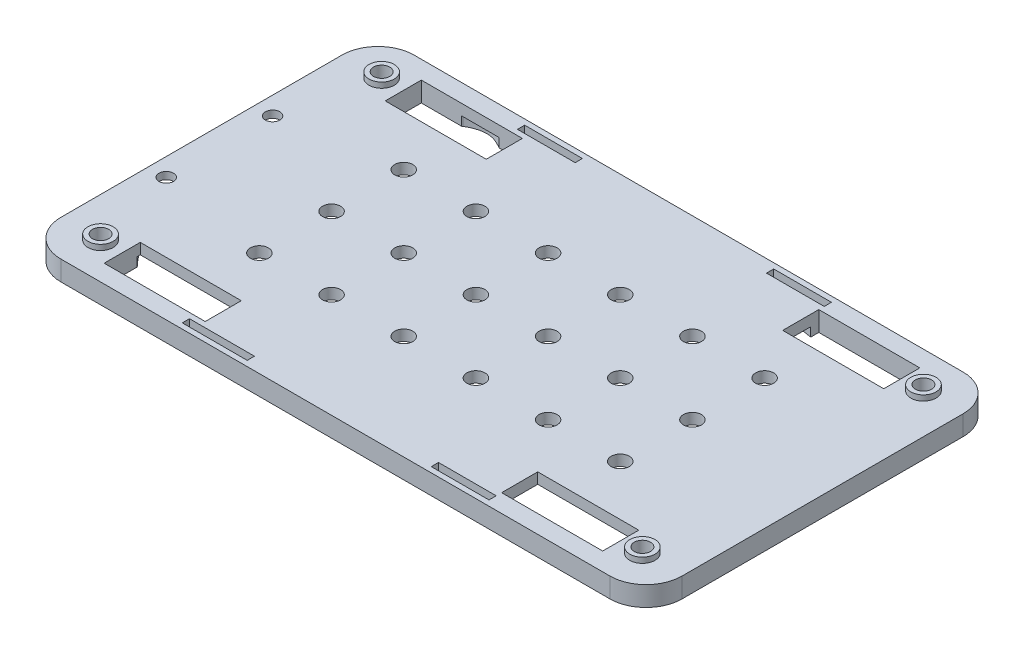
SolidWorks part; units mm, degrees
ref_plane "Front Plane" through (0, 0, 0) normal (0, 0, 1) x (1, 0, 0)
ref_plane "Top Plane" through (0, 0, 0) normal (0, 1, 0) x (1, 0, 0)
ref_plane "Right Plane" through (0, 0, 0) normal (1, 0, 0) x (0, 0, -1)
sketch "Sketch1" plane through (0, 0, 0) normal (0, 1, 0) x (1, 0, 0)
  line L1 (-78.1571, 35.933) -> (-78.1571, -14.1122)
  line L2 (78.9797, 0.0343) -> (-78.1571, 0.0343) construction
  line L3 (-77.1571, 35.7646) -> (-77.1571, -14.1122)
  line L4 (78.9797, -0.9657) -> (-78.1571, -0.9657)
  arc A1 (37.8695, -35.2975) -> (39.5975, -35.2134) centre (38.2635, -25.6055) ccw
  arc A2 (37.9263, -34.299) -> (39.4753, -34.2207) centre (38.2635, -25.6055) ccw
  spline S0 degree 1 poles (-77.1571, -14.1122) (-56.919, -31.9168) knots 0 0 1 1 construction
  spline S1 degree 1 poles (-56.919, -31.9168) (37.9263, -34.299) knots 0 0 1 1 construction
  spline S2 degree 1 poles (39.4753, -34.2207) (77.9849, 0.1477) knots 0 0 1 1 construction
  spline S3 degree 1 poles (77.9849, 0.1477) (25.0602, 52.8732) knots 0 0 1 1 construction
  spline S4 degree 1 poles (25.0602, 52.8732) (-5.6593, 44.1904) knots 0 0 1 1 construction
  spline S5 degree 1 poles (-5.6593, 44.1904) (-43.9853, 50.6886) knots 0 0 1 1 construction
  spline S6 degree 1 poles (-43.9853, 50.6886) (-59.7702, 54.7238) knots 0 0 1 1 construction
  spline S7 degree 1 poles (-59.7702, 54.7238) (-74.5158, 41.0521) knots 0 0 1 1 construction
  spline S8 degree 1 poles (-74.5158, 41.0521) (-77.1571, 35.7646) knots 0 0 1 1 construction
  spline S9 degree 3 poles (-77.1571, -14.1122) (-77.1565, -14.3701) (-77.1092, -14.8732) (-76.8359, -15.9559) (-76.1879, -17.5008) (-75.044, -19.4183) (-73.152, -22.0092) (-70.3495, -25.0822) (-66.8736, -28.0972) (-63.6864, -30.2141) (-61.0019, -31.4062) (-58.8274, -31.848) (-57.5718, -31.8794) (-56.919, -31.9168) knots 0.000484 0.000484 0.000484 0.000484 0.031521 0.062558 0.124632 0.186706 0.248781 0.372929 0.497077 0.621225 0.745373 0.869521 0.993669 0.993669 0.993669 0.993669
  spline S10 degree 3 poles (-56.919, -31.9168) (-56.6769, -31.8873) (-56.2021, -31.8274) (-55.1791, -31.687) (-53.8294, -31.4877) (-52.0759, -31.2184) (-49.5744, -30.8354) (-46.1465, -30.3372) (-41.5825, -29.7813) (-36.5976, -29.3261) (-29.4274, -28.913) (-19.5571, -28.8468) (-6.4839, -29.5875) (5.2448, -30.7865) (15.023, -31.9295) (22.521, -32.809) (30.1538, -33.642) (35.3408, -34.1075) (37.9263, -34.299) knots 0.000538 0.000538 0.000538 0.000538 0.016152 0.031766 0.062993 0.094221 0.125449 0.187904 0.250359 0.312815 0.37527 0.50018 0.625091 0.750001 0.812457 0.874912 0.937367 0.999822 0.999822 0.999822 0.999822
  spline S11 degree 3 poles (39.4753, -34.2207) (41.0079, -34.0574) (44.09, -33.7147) (50.0835, -32.8429) (57.0969, -31.1859) (64.2184, -27.8839) (69.7763, -23.1857) (73.0497, -18.2789) (74.9177, -14.0269) (75.9805, -10.7732) (76.7509, -7.5724) (77.1995, -5.064) (77.4798, -3.2279) (77.6607, -1.9649) (77.8261, -0.8108) (77.9301, -0.1834) (77.9849, 0.1477) knots -0.000309 -0.000309 -0.000309 -0.000309 0.063093 0.126495 0.253299 0.380104 0.506908 0.633712 0.697114 0.760516 0.823918 0.88732 0.919021 0.950722 0.982423 1.014124 1.014124 1.014124 1.014124
  spline S12 degree 3 poles (77.9849, 0.1477) (78.0286, 1.2633) (78.0637, 3.5224) (77.9426, 6.757) (77.6596, 9.9047) (77.0733, 13.9671) (75.9626, 18.7836) (73.4433, 25.9357) (69.0206, 33.8098) (62.0495, 41.4932) (53.7895, 47.3444) (44.6121, 51.2947) (34.9036, 53.2804) (28.3113, 53.2357) (25.0602, 52.8732) knots 0.000169 0.000169 0.000169 0.000169 0.031414 0.062658 0.093902 0.125147 0.187635 0.250124 0.375101 0.500079 0.625056 0.750034 0.875011 0.999988 0.999988 0.999988 0.999988
  spline S13 degree 3 poles (25.0602, 52.8732) (19.8954, 51.6294) (12.3224, 49.1317) (2.1607, 45.9713) (-3.0371, 44.6913) (-5.6593, 44.1904) knots 0.000659 0.000659 0.000659 0.000659 0.498067 0.746772 0.995476 0.995476 0.995476 0.995476
  spline S14 degree 3 poles (-5.6593, 44.1904) (-6.6879, 44.0461) (-8.7287, 43.7719) (-12.9633, 43.2668) (-18.1826, 42.7952) (-23.9015, 42.6322) (-28.8306, 42.9899) (-32.9666, 43.9514) (-35.9177, 45.2914) (-38.1959, 46.6779) (-39.9392, 47.8658) (-41.507, 48.9798) (-42.8638, 49.9292) (-43.6163, 50.4405) (-43.9853, 50.6886) knots -0.000196 -0.000196 -0.000196 -0.000196 0.062587 0.12537 0.250936 0.376501 0.502067 0.627632 0.753198 0.815981 0.878764 0.941546 0.972938 1.004329 1.004329 1.004329 1.004329
  spline S15 degree 3 poles (-43.9853, 50.6886) (-44.2445, 50.8673) (-44.7682, 51.2325) (-45.7507, 51.9331) (-46.8912, 52.7591) (-48.146, 53.6496) (-49.6971, 54.6811) (-51.4608, 55.6487) (-53.4077, 56.2593) (-55.2517, 56.3574) (-56.711, 56.0808) (-57.7948, 55.7138) (-58.5465, 55.3915) (-59.2299, 55.0428) (-59.5837, 54.8359) (-59.7702, 54.7238) knots -0.002497 -0.002497 -0.002497 -0.002497 0.029066 0.060629 0.123754 0.18688 0.250006 0.376257 0.502509 0.62876 0.755012 0.818137 0.881263 0.944389 1.007515 1.007515 1.007515 1.007515
  spline S16 degree 3 poles (-78.1571, -14.1122) (-78.1559, -14.7524) (-77.9173, -15.9777) (-77.0678, -17.9828) (-75.8538, -20.0098) (-73.8827, -22.6985) (-70.9901, -25.8584) (-67.4096, -28.9504) (-64.0991, -31.1349) (-61.2379, -32.3904) (-59.243, -32.7789) (-57.8421, -32.8756) (-57.2118, -32.9007) (-56.8882, -32.9203) knots 0.000409 0.000409 0.000409 0.000409 0.062843 0.125276 0.18771 0.250143 0.375011 0.499878 0.624745 0.749612 0.874479 0.936913 0.999346 0.999346 0.999346 0.999346
  spline S17 degree 3 poles (-56.8882, -32.9203) (-56.6427, -32.8908) (-56.1603, -32.8306) (-55.1309, -32.6904) (-53.7754, -32.491) (-52.0233, -32.2221) (-49.5292, -31.8398) (-46.1189, -31.3427) (-41.5829, -30.7872) (-36.6286, -30.3313) (-29.4997, -29.9158) (-19.6749, -29.8441) (-6.6369, -30.5782) (5.0856, -31.7749) (14.8757, -32.919) (22.3927, -33.8009) (30.0532, -34.6371) (35.2704, -35.1052) (37.8695, -35.2975) knots -0.001373 -0.001373 -0.001373 -0.001373 0.014273 0.029919 0.06121 0.092502 0.123794 0.186377 0.24896 0.311543 0.374127 0.499293 0.62446 0.749626 0.81221 0.874793 0.937376 0.99996 0.99996 0.99996 0.99996
  spline S18 degree 3 poles (39.5975, -35.2134) (41.1398, -35.049) (44.2356, -34.7045) (50.3018, -33.8209) (57.4502, -32.1301) (64.7991, -28.7164) (70.5782, -23.8111) (73.9656, -18.7006) (75.8832, -14.3057) (76.9672, -10.962) (77.7479, -7.6914) (78.1997, -5.145) (78.4804, -3.2966) (78.6613, -2.0308) (78.824, -0.9009) (78.9276, -0.2806) (78.9816, 0.0458) knots -0.000086 -0.000086 -0.000086 -0.000086 0.063428 0.126941 0.253967 0.380993 0.50802 0.635046 0.698559 0.762072 0.825585 0.889098 0.920855 0.952612 0.984368 1.016125 1.016125 1.016125 1.016125
  spline S19 degree 3 poles (78.9816, 0.0458) (79.0271, 1.1797) (79.0647, 3.4739) (78.9444, 6.7697) (78.6587, 9.9749) (78.0642, 14.1169) (76.9341, 19.0326) (74.3646, 26.3398) (69.8439, 34.3944) (62.712, 42.2543) (54.2626, 48.2351) (44.8799, 52.2671) (34.9529, 54.2886) (28.2109, 54.2351) (24.8869, 53.8601) knots -0.000407 -0.000407 -0.000407 -0.000407 0.03088 0.062166 0.093453 0.12474 0.187314 0.249888 0.375035 0.500183 0.62533 0.750478 0.875625 1.000773 1.000773 1.000773 1.000773
  spline S20 degree 3 poles (24.8869, 53.8601) (22.2839, 53.2349) (17.1223, 51.77) (6.9788, 48.4835) (-0.6206, 46.1711) (-5.8226, 45.1772) knots -0.001281 -0.001281 -0.001281 -0.001281 0.247714 0.49671 0.9947 0.9947 0.9947 0.9947
  spline S21 degree 3 poles (-5.8226, 45.1772) (-6.8463, 45.0337) (-8.8779, 44.761) (-13.0882, 44.2593) (-18.2643, 43.7927) (-23.9018, 43.6338) (-28.7026, 43.9859) (-32.6523, 44.9085) (-35.4477, 46.177) (-37.6484, 47.5152) (-39.3619, 48.6824) (-40.9248, 49.793) (-42.292, 50.7496) (-43.0505, 51.2651) (-43.4225, 51.5151) knots 0.000305 0.000305 0.000305 0.000305 0.063048 0.125791 0.251276 0.376761 0.502247 0.627732 0.753218 0.815961 0.878703 0.941446 0.972817 1.004189 1.004189 1.004189 1.004189
  spline S22 degree 3 poles (-43.4225, 51.5151) (-43.6786, 51.6918) (-44.1958, 52.0526) (-45.1684, 52.7462) (-46.308, 53.5714) (-47.577, 54.4721) (-49.1727, 55.5335) (-51.0441, 56.5648) (-53.2147, 57.2519) (-55.3195, 57.3652) (-56.9568, 57.0533) (-58.1477, 56.6506) (-58.9689, 56.2985) (-59.5708, 55.992) (-60.0059, 55.7483) (-60.1862, 55.6406) (-60.2803, 55.5839) knots -0.002294 -0.002294 -0.002294 -0.002294 0.029245 0.060783 0.12386 0.186936 0.250013 0.376167 0.50232 0.628473 0.754627 0.817704 0.88078 0.943857 0.975396 1.006934 1.006934 1.006934 1.006934
  spline S23 degree 3 poles (-60.2803, 55.5839) (-60.715, 55.3297) (-61.582, 54.801) (-63.2222, 53.7187) (-65.9105, 51.7373) (-69.2431, 48.741) (-72.0244, 45.6929) (-73.7392, 43.6279) (-74.6657, 42.4756) (-75.1049, 41.9202) (-75.3265, 41.639) knots 0.000427 0.000427 0.000427 0.000427 0.063268 0.126109 0.251792 0.503158 0.754524 0.880206 0.943048 1.005889 1.005889 1.005889 1.005889
  spline S24 degree 3 poles (-59.7702, 54.7238) (-60.1936, 54.4761) (-61.0386, 53.9612) (-62.6368, 52.9072) (-65.2587, 50.9763) (-68.5171, 48.0498) (-71.2443, 45.0657) (-73.1899, 42.7247) (-74.0698, 41.6179) (-74.5158, 41.0521) knots 0.000174 0.000174 0.000174 0.000174 0.062881 0.125589 0.251004 0.501833 0.752662 0.878077 1.003492 1.003492 1.003492 1.003492
  spline S25 degree 3 poles (-74.5158, 41.0521) (-75.0658, 40.2217) (-76.0765, 38.4779) (-76.8336, 36.6875) (-77.1571, 35.7646) knots 0.499549 0.499549 0.499549 0.499549 0.499766 0.499983 0.499983 0.499983 0.499983
  spline S26 degree 3 poles (-75.3265, 41.639) (-75.92, 40.746) (-77.0064, 38.8701) (-77.815, 36.9314) (-78.1571, 35.933) knots 0.499546 0.499546 0.499546 0.499546 0.49977 0.499995 0.499995 0.499995 0.499995
  point P0 (0.4631, 0.0343)
  dimension "D1" = 1
sketch "Sketch6" plane through (0, 0, 0) normal (0, 1, 0) x (1, 0, 0)
  line L0 (-78.1571, 35.933) -> (-78.1571, -14.1122) construction
  line L1 (73.9816, 59.5839) -> (-78.1571, 59.5839)
  line L2 (83.9816, 49.5839) -> (83.9816, -28.2975)
  line L3 (73.9816, -38.2975) -> (-78.1571, -38.2975)
  line L4 (-88.1571, 49.5839) -> (-88.1571, -28.2975)
  arc A0 (-78.1571, -38.2975) -> (-88.1571, -28.2975) centre (-78.1571, -28.2975) cw
  arc A1 (-88.1571, 49.5839) -> (-78.1571, 59.5839) centre (-78.1571, 49.5839) cw
  arc A2 (73.9816, 59.5839) -> (83.9816, 49.5839) centre (73.9816, 49.5839) cw
  arc A3 (83.9816, -28.2975) -> (73.9816, -38.2975) centre (73.9816, -28.2975) cw
  dimension "D5" = 10
  dimension "D1" = 5
  dimension "D2" = 10
  dimension "D3" = 3
  dimension "D4" = 4
extrude "Boss-Extrude2" add sketch "Sketch6" along normal blind 6.5
extrude "Cut-Extrude1" cut sketch "Sketch1" along normal blind 2.5 contours A2 S11 L4 L3 S9 S10 | S24 S25 L3 L4 S11 S12 S13 S14 S15 region at (0.1139, 0, 15.5782) region at (-2.2602, 0, -23.2786)
sketch "Sketch7" plane through (0, 0, 0) normal (0, -1, 0) x (1, 0, 0)
  line L1 (-76.2189, 14.1122) -> (-91.3452, 14.1122)
  line L2 (-76.2189, 14.1122) -> (-76.2189, -35.933)
  line L3 (-76.2189, -35.933) -> (-91.3452, -35.933)
  line L4 (-91.3452, 14.1122) -> (-91.3452, -35.933)
extrude "Cut-Extrude2" cut sketch "Sketch7" against normal up to surface (2.5 mm away) contours L2 L1 L4 L3 up to face at (-19.4492, 2.5, -12.7234)
sketch "Sketch8" plane through (0, 6.5, 0) normal (0, 1, 0) x (1, 0, 0)
  line L0 (83.9816, 10.6432) -> (-88.1571, 10.6432) construction
  line L1 (83.9816, -28.2975) -> (83.9816, 49.5839) construction
  line L2 (-88.1571, 49.5839) -> (-88.1571, -28.2975) construction
  line L3 (-2.0877, 59.5839) -> (-2.0877, -38.2975) construction
  line L4 (73.9816, 59.5839) -> (-78.1571, 59.5839) construction
  line L5 (-78.1571, -38.2975) -> (73.9816, -38.2975) construction
  line L7 (78.9816, 54.5839) -> (38.9816, 54.5839)
  line L8 (78.9816, 54.5839) -> (78.9816, 44.5839)
  line L9 (78.9816, 44.5839) -> (38.9816, 44.5839)
  line L10 (38.9816, 54.5839) -> (38.9816, 44.5839)
  line L22 (38.9816, 49.5839) -> (78.9816, 49.5839) construction
  line L23 (66.9816, 54.5839) -> (66.9816, 44.5839)
  circle A1 centre (72.9816, 49.5839) radius 3.5
  dimension "D6" = 7
  dimension "D1" = 10
  dimension "D2" = 40
  dimension "D3" = 5
  dimension "D4" = 5
  dimension "D5" = 6
  dimension "D7" = 6
sketch "Sketch9" plane through (0, 0, 0) normal (0, -1, 0) x (1, 0, 0)
  circle A0 centre (72.9816, -49.5839) radius 4.5
  dimension "D1" = 9
extrude "Cut-Extrude5" cut sketch "Sketch9" against normal blind 3.5
sketch "Sketch10" plane through (0, 3.5, 0) normal (0, -1, 0) x (1, 0, 0)
  circle A0 centre (72.9816, -49.5839) radius 2.25
  dimension "D1" = 4.5
extrude "Cut-Extrude6" cut sketch "Sketch10" against normal blind 21
extrude "Cut-Extrude8" cut sketch "Sketch8" against normal blind 42 contours L23 L7 L10 L9 region at (52.9816, 6.5, -49.5839)
extrude "Cut-Extrude9" cut sketch "Sketch8<3>" against normal blind 1 contours L7 L23 L9 L8 A1 region at (78.8254, 6.5, -49.5839)
sketch "Sketch8<3>" plane through (0, 6.5, 0) normal (0, 1, 0) x (1, 0, 0) same geometry as "Sketch8"
sketch "Sketch12" plane through (0, 6.5, 0) normal (0, 1, 0) x (1, 0, 0)
  line L0 (-88.1571, 10.6432) -> (83.9816, 10.6432) construction
  line L1 (-88.1571, 49.5839) -> (-88.1571, -28.2975) construction
  line L2 (83.9816, -28.2975) -> (83.9816, 49.5839) construction
  line L3 (-2.0877, 59.5839) -> (-2.0877, -36.8461) construction
  line L4 (73.9816, 59.5839) -> (-78.1571, 59.5839) construction
ref_plane "Plane1" through (0, 0, -10.6432) normal (0, 0, 1) x (1, 0, 0)
ref_plane "Plane2" through (-2.0877, 0, 0) normal (-1, 0, 0) x (0, 0, 1)
mirror "Mirror1" about plane through (0, 0, -10.6432) normal (0, 0, 1) of "Cut-Extrude5", "Cut-Extrude6", "Cut-Extrude8", "Cut-Extrude9"
mirror "Mirror2" about plane through (-2.0877, 0, 0) normal (-1, 0, 0) of "Mirror1", "Cut-Extrude9", "Cut-Extrude8", "Cut-Extrude6", "Cut-Extrude5"
sketch "Sketch13" plane through (0, 6.5, 0) normal (0, 1, 0) x (1, 0, 0)
  line L0 (-83.1571, 44.5839) -> (-43.1571, 44.5839) construction
  line L1 (58.9816, 39.5839) -> (-63.1571, 39.5839)
  line L2 (58.9816, 39.5839) -> (58.9816, -18.2975)
  line L3 (58.9816, -18.2975) -> (-63.1571, -18.2975)
  line L4 (-63.1571, 39.5839) -> (-63.1571, -18.2975)
  line L5 (58.9816, 39.5839) -> (-63.1571, -18.2975) construction
  line L6 (58.9816, -18.2975) -> (-63.1571, 39.5839) construction
  line L7 (-83.1571, -23.2975) -> (-43.1571, -23.2975) construction
  line L8 (83.9816, -28.2975) -> (83.9816, 49.5839) construction
  line L9 (-88.1571, 49.5839) -> (-88.1571, -28.2975) construction
  point P0 (-2.0877, 10.6432)
  dimension "D1" = 5
  dimension "D2" = 5
  dimension "D3" = 25
  dimension "D4" = 25
extrude "Cut-Extrude10" cut sketch "Sketch13" against normal blind 1
sketch "Sketch14" plane through (0, 5.5, 0) normal (0, 1, 0) x (1, 0, 0)
  line L0 (-63.1571, 10.6432) -> (58.9816, 10.6432) construction
  line L1 (-63.1571, 39.5839) -> (-63.1571, -18.2975) construction
  line L2 (58.9816, -18.2975) -> (58.9816, 39.5839) construction
  line L3 (-63.1571, -9.3568) -> (58.9816, -9.3568) construction
  line L4 (-63.1571, 10.6432) -> (58.9816, 10.6432) construction
  line L5 (-63.1571, 30.6432) -> (58.9816, 30.6432) construction
  circle A1 centre (-12.0877, 10.6432) radius 2.5
  circle A2 centre (-32.0877, 10.6432) radius 2.5
  circle A3 centre (-52.0877, 10.6432) radius 2.5
  circle A4 centre (-12.0877, 10.6432) radius 2.5
  circle A5 centre (-32.0877, 10.6432) radius 2.5
  circle A6 centre (7.9123, 10.6432) radius 2.5
  circle A7 centre (-12.0877, 10.6432) radius 2.5
  circle A8 centre (27.9123, 10.6432) radius 2.5
  circle A9 centre (7.9123, 10.6432) radius 2.5
  circle A10 centre (7.9123, 10.6432) radius 2.5
  circle A11 centre (27.9123, 10.6432) radius 2.5
  circle A12 centre (47.9123, 10.6432) radius 2.5
  circle A13 centre (-12.0877, -9.3568) radius 2.5
  circle A14 centre (-32.0877, -9.3568) radius 2.5
  circle A15 centre (-52.0877, -9.3568) radius 2.5
  circle A16 centre (-12.0877, -9.3568) radius 2.5
  circle A17 centre (-32.0877, -9.3568) radius 2.5
  circle A18 centre (7.9123, -9.3568) radius 2.5
  circle A19 centre (-12.0877, -9.3568) radius 2.5
  circle A20 centre (27.9123, -9.3568) radius 2.5
  circle A21 centre (7.9123, -9.3568) radius 2.5
  circle A22 centre (7.9123, -9.3568) radius 2.5
  circle A23 centre (27.9123, -9.3568) radius 2.5
  circle A24 centre (47.9123, -9.3568) radius 2.5
  circle A25 centre (-12.0877, 10.6432) radius 2.5
  circle A26 centre (-32.0877, 10.6432) radius 2.5
  circle A27 centre (-52.0877, 10.6432) radius 2.5
  circle A28 centre (-12.0877, 10.6432) radius 2.5
  circle A29 centre (-32.0877, 10.6432) radius 2.5
  circle A30 centre (7.9123, 10.6432) radius 2.5
  circle A31 centre (-12.0877, 10.6432) radius 2.5
  circle A32 centre (27.9123, 10.6432) radius 2.5
  circle A33 centre (7.9123, 10.6432) radius 2.5
  circle A34 centre (7.9123, 10.6432) radius 2.5
  circle A35 centre (27.9123, 10.6432) radius 2.5
  circle A36 centre (47.9123, 10.6432) radius 2.5
  circle A37 centre (-12.0877, 30.6432) radius 2.5
  circle A38 centre (-32.0877, 30.6432) radius 2.5
  circle A39 centre (-52.0877, 30.6432) radius 2.5
  circle A40 centre (-12.0877, 30.6432) radius 2.5
  circle A41 centre (-32.0877, 30.6432) radius 2.5
  circle A42 centre (7.9123, 30.6432) radius 2.5
  circle A43 centre (-12.0877, 30.6432) radius 2.5
  circle A44 centre (27.9123, 30.6432) radius 2.5
  circle A45 centre (7.9123, 30.6432) radius 2.5
  circle A46 centre (7.9123, 30.6432) radius 2.5
  circle A47 centre (27.9123, 30.6432) radius 2.5
  circle A48 centre (47.9123, 30.6432) radius 2.5
  point P8 (-2.0877, 10.6432)
  point P37 (-2.0877, -9.3568)
  point P64 (-2.0877, 10.6432)
  point P91 (-2.0877, 30.6432)
  dimension "D2" = 5
  dimension "D1" = 10
  dimension "D3" = 3
  dimension "D4" = 4
  dimension "D5" = 2
  dimension "D6" = 2
extrude "Cut-Extrude11" cut sketch "Sketch14" against normal blind 57 contours A39 | A42 | A44 | A48 | A12 | A6 | A1 | A2 | A3 | A24 | A20 | A18 | A13 | A14 | A15 | A38 | A37 | A8 region at (-12.0877, 5.5, -10.6432) region at (-32.0877, 5.5, -10.6432) region at (-52.0877, 5.5, -10.6432) region at (7.9123, 5.5, -10.6432) region at (47.9123, 5.5, -10.6432) region at (-12.0877, 5.5, 9.3568) region at (-32.0877, 5.5, 9.3568) region at (-52.0877, 5.5, 9.3568) region at (7.9123, 5.5, 9.3568) region at (27.9123, 5.5, 9.3568) region at (47.9123, 5.5, 9.3568) region at (-52.0877, 5.5, -30.6432) region at (7.9123, 5.5, -30.6432) region at (27.9123, 5.5, -30.6432) region at (47.9123, 5.5, -30.6432)
sketch "Sketch16" plane through (0, 0, 0) normal (0, -1, 0) x (1, 0, 0)
  line L0 (78.9816, -0.5458) -> (78.9816, -79.1994) construction
  line L1 (22.9816, -56.0839) -> (-37.6427, -56.0839) construction
  line L2 (73.9816, -59.5839) -> (-78.1571, -59.5839) construction
  line L3 (38.9816, -54.3238) -> (38.9816, 38.2975) construction
  line L4 (38.9816, -59.5839) -> (38.9816, -54.3238) construction
  line L5 (38.9816, -56.0839) -> (22.9816, -56.0839)
  line L6 (38.9816, -56.0839) -> (38.9816, -58.0839)
  line L7 (38.9816, -58.0839) -> (22.9816, -58.0839)
  line L8 (22.9816, -56.0839) -> (22.9816, -58.0839)
  line L9 (-78.1571, 38.2975) -> (73.9816, 38.2975) construction
  line L10 (22.9816, -56.0839) -> (22.9816, 38.2975) construction
  line L12 (38.9816, 36.7975) -> (22.9816, 36.7975)
  line L13 (38.9816, 36.7975) -> (38.9816, 34.7975)
  line L14 (38.9816, 34.7975) -> (22.9816, 34.7975)
  line L15 (22.9816, 36.7975) -> (22.9816, 34.7975)
  line L16 (22.9816, 34.7975) -> (-46.0184, 34.7975) construction
  line L17 (-30.0184, -56.0839) -> (-46.0184, -56.0839)
  line L18 (-30.0184, -56.0839) -> (-30.0184, -58.0839)
  line L19 (-30.0184, -58.0839) -> (-46.0184, -58.0839)
  line L20 (-46.0184, -56.0839) -> (-46.0184, -58.0839)
  line L22 (-28.0184, 34.7975) -> (-46.0184, 34.7975)
  line L23 (-28.0184, 34.7975) -> (-28.0184, 36.7975)
  line L24 (-28.0184, 36.7975) -> (-46.0184, 36.7975)
  line L25 (-46.0184, 34.7975) -> (-46.0184, 36.7975)
  dimension "D1" = 40
  dimension "D2" = 16
  dimension "D3" = 1.5
  dimension "D4" = 2
  dimension "D5" = 2
  dimension "D6" = 1.5
  dimension "D7" = 125
  dimension "D8" = 16
  dimension "D9" = 2
  dimension "D10" = 18
  dimension "D11" = 2
extrude "Cut-Extrude12" cut sketch "Sketch16" against normal blind 57
sketch "Sketch17" plane through (0, 5.5, 0) normal (0, 1, 0) x (1, 0, 0)
  line L1 (-99.5963, 69.0247) -> (98.4238, 69.0247)
  line L2 (-99.5963, 69.0247) -> (-99.5963, -53.2143)
  line L3 (-99.5963, -53.2143) -> (98.4238, -53.2143)
  line L4 (98.4238, 69.0247) -> (98.4238, -53.2143)
extrude "Cut-Extrude14" cut sketch "Sketch17" along normal blind 48.5
sketch "Sketch23" plane through (0, 2.5, 0) normal (0, -1, 0) x (1, 0, 0)
  line L0 (-88.1571, -10.9104) -> (-64.7808, -10.9104) construction
  line L1 (-88.1571, -35.933) -> (-88.1571, 14.1122) construction
  circle A0 centre (-83.1571, 4.0896) radius 2
  circle A1 centre (-83.1571, 4.0896) radius 4.25
  dimension "D1" = 4
  dimension "D4" = 8.5
  dimension "D2" = 15
  dimension "D3" = 5
extrude "Cut-Extrude15" cut sketch "Sketch23" against normal blind 48.5 contours A0
extrude "Cut-Extrude16" cut sketch "Sketch23<3>" against normal blind 1
sketch "Sketch23<3>" plane through (0, 2.5, 0) normal (0, -1, 0) x (1, 0, 0) same geometry as "Sketch23"
mirror "Mirror4" about plane through (0, 0, -10.6432) normal (0, 0, 1) of "Cut-Extrude16", "Cut-Extrude15"
sketch "Sketch25" plane through (0, 5.5, 0) normal (0, 1, 0) x (1, 0, 0)
  circle A0 centre (72.9816, 49.5839) radius 2.25
  circle A1 centre (72.9816, 49.5839) radius 3.5
  circle A2 centre (72.9816, -28.2975) radius 2.25
  circle A3 centre (72.9816, -28.2975) radius 3.5
  circle A4 centre (-77.1571, 49.5839) radius 2.25
  circle A5 centre (-77.1571, 49.5839) radius 3.5
  circle A6 centre (-77.1571, -28.2975) radius 2.25
  circle A7 centre (-77.1571, -28.2975) radius 3.5
  dimension "D1" = 7
  dimension "D2" = 7
  dimension "D3" = 7
  dimension "D4" = 7
extrude "Boss-Extrude3" add sketch "Sketch25" along normal blind 1.5
